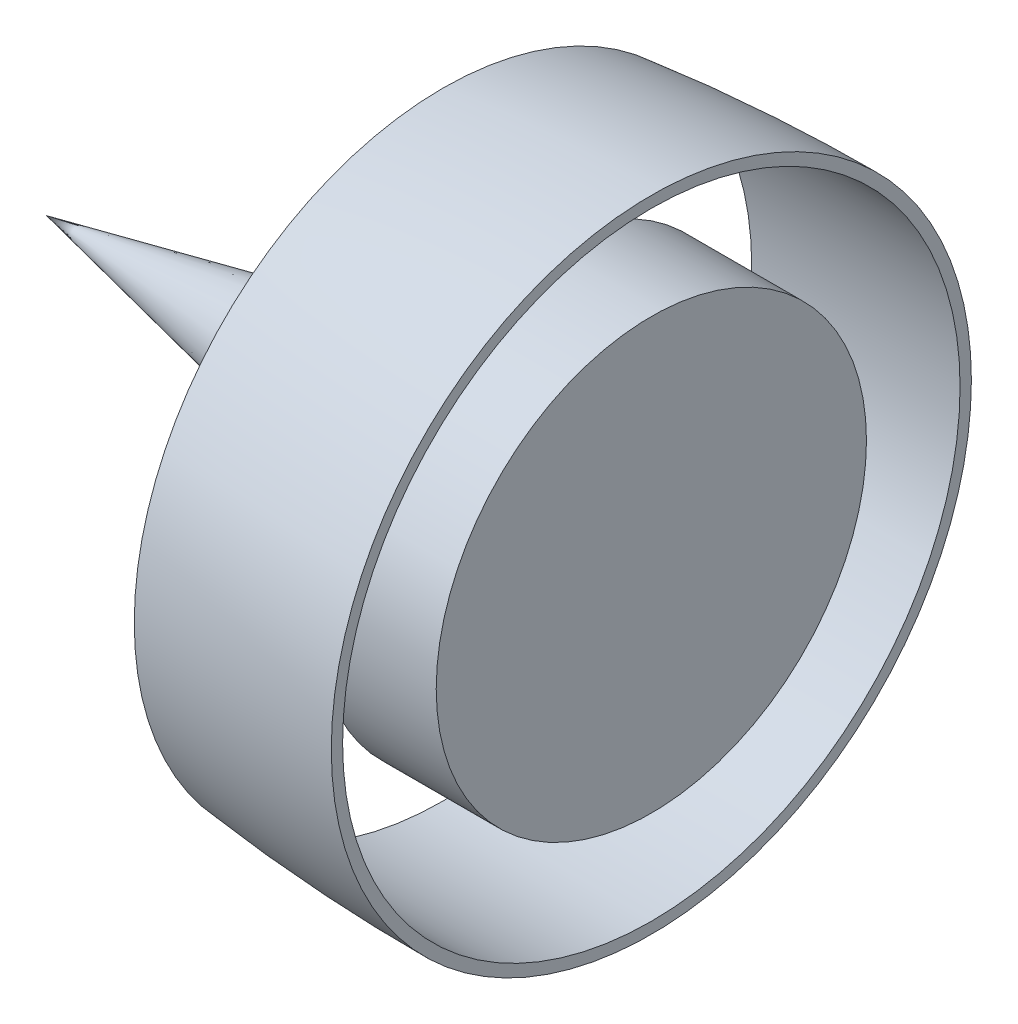
SolidWorks part; units mm, degrees
ref_plane "Piano frontale" through (0, 0, 0) normal (0, 0, 1) x (1, 0, 0)
ref_plane "Piano superiore" through (0, 0, 0) normal (0, 1, 0) x (1, 0, 0)
ref_plane "Piano destro" through (0, 0, 0) normal (1, 0, 0) x (0, 0, -1)
sketch "Schizzo1" plane through (0, 0, 0) normal (0, 0, 1) x (1, 0, 0)
  line L0 (0, 0) -> (428.2336, 89.4627)
  line L1 (428.2336, 89.4627) -> (692.9983, 219.743)
  line L2 (692.9983, 219.743) -> (852.5315, 373.2653)
  line L3 (0, 0) -> (428.2336, 89.4627)
  line L4 (0, 0) -> (852.5315, 0)
  line L5 (852.5315, 0) -> (852.5315, 373.2653) construction
  line L6 (0, 0) -> (693.3334, 538.6966) construction
  line L7 (693.3334, 538.6966) -> (428.2336, 89.4627) construction
  line L8 (852.5315, 373.2653) -> (693.3334, 538.6966) construction
  line L9 (693.3334, 538.6966) -> (692.9983, 219.743) construction
  line L10 (852.5315, 373.2653) -> (859.737, 380.1993)
  line L11 (693.3334, 538.6966) -> (700.5389, 545.6307) construction
  line L12 (700.5389, 545.6307) -> (859.737, 380.1993) construction
  line L13 (859.737, 380.1993) -> (1068.7431, 380.1993)
  line L14 (1068.7431, 380.1993) -> (1068.7431, 0)
  line L15 (1068.7431, 0) -> (852.5315, 0)
  line L16 (700.5389, 545.6307) -> (1068.7431, 545.6307)
  line L17 (496.218, 565.6307) -> (50496.218, 565.6307) construction
  line L19 (1068.7431, 565.6307) -> (1068.7431, 545.6307)
  line L20 (-275.0185, 0) -> (49724.9815, 0) construction
  arc A0 (700.5389, 545.6307) -> (1068.7431, 565.6307) centre (1068.7431, -2833.7282) cw
  dimension "D1" = 11.8
  dimension "D2" = 26.2
  dimension "D3" = 43.9
  dimension "D4" = 26.046
  dimension "D5" = 33.255
  dimension "D6" = 46.04
  dimension "D7" = 229.59
  dimension "D8" = 10
  dimension "D9" = 20
  dimension "D10" = 216.2116
revolve "Rivoluzione1" add sketch "Schizzo1" angle 360 about L20 region at (764.9072, 140.8951, 0) region at (930.6122, 553.6327, 0)
